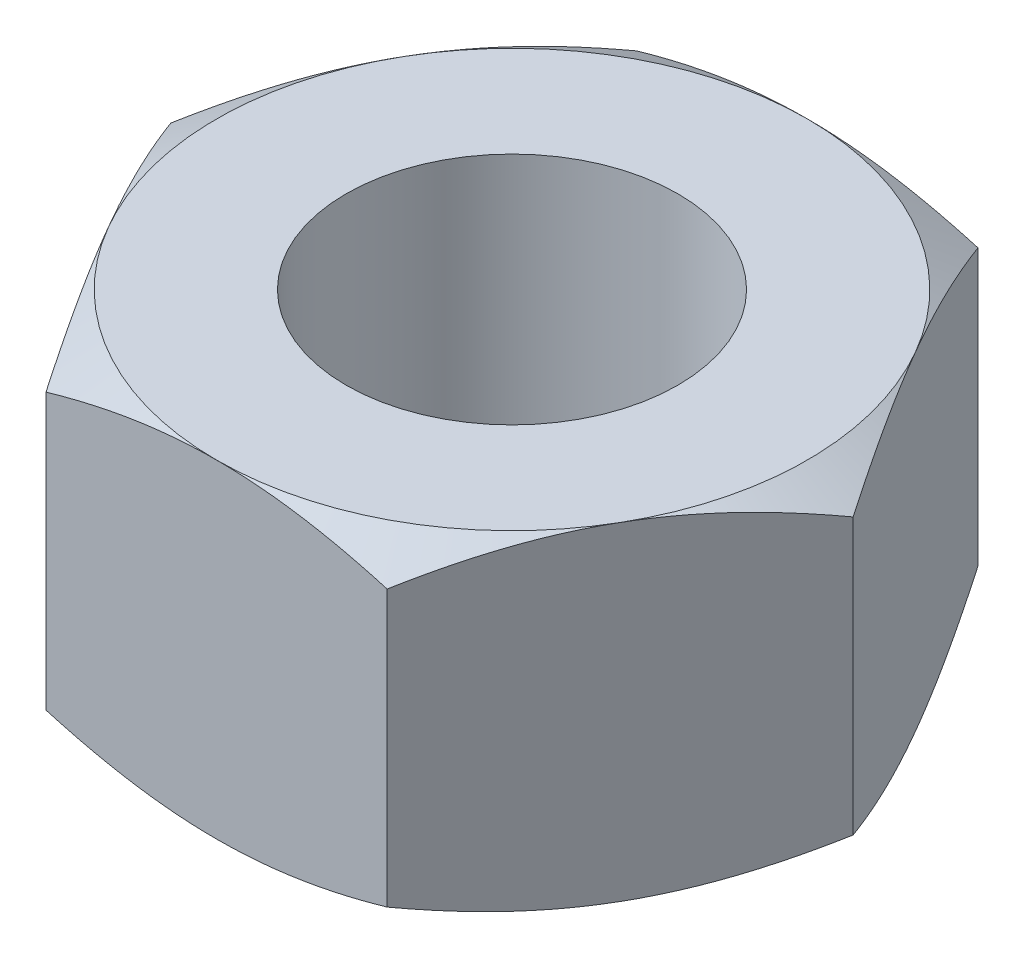
SolidWorks part; units mm, degrees
ref_plane "Front Plane" through (0, 0, 0) normal (0, 0, 1) x (1, 0, 0)
ref_plane "Top Plane" through (0, 0, 0) normal (0, 1, 0) x (1, 0, 0)
ref_plane "Right Plane" through (0, 0, 0) normal (1, 0, 0) x (0, 0, -1)
ref_axis "Axis_X" through (-88.99, 0, 0) along (1, 0, 0)
ref_axis "Axis_Y" through (0, 55, 0) along (0, -1, 0)
ref_axis "Axis_Z" through (0, 0, -88.99) along (0, 0, 1)
sketch "Sketch1" plane through (0, 0, 0) normal (0, 1, 0) x (1, 0, 0)
  line L1 (5.1962, 9) -> (-5.1962, 9)
  line L2 (-5.1962, 9) -> (-10.3923, 0)
  line L3 (-10.3923, 0) -> (-5.1962, -9)
  line L4 (-5.1962, -9) -> (5.1962, -9)
  line L5 (5.1962, -9) -> (10.3923, 0)
  line L6 (10.3923, 0) -> (5.1962, 9)
  circle A0 centre (0, 0) radius 9 construction
  circle A1 centre (0, 0) radius 5.053
  dimension "FIX_4" = 10.106
  dimension "FIX_1" = 18
extrude "Boss-Extrude1" add sketch "Sketch1" along normal blind 10
cosmetic thread "Thread1" parameters "D2"=12
sketch "Sketch2" plane through (0, 0, 0) normal (0, 0, 1) x (1, 0, 0)
  line L0 (-10.3923, 0.8038) -> (-10.3923, 0)
  line L1 (-10.3923, 10) -> (-10.3923, 0) construction
  line L2 (-10.3923, 0) -> (-9, 0)
  line L3 (-5.1962, 0) -> (-10.3923, 0) construction
  line L4 (-9, 0) -> (-10.3923, 0.8038)
  line L7 (-10.3923, 10) -> (-10.3923, 9.1962)
  line L8 (-10.3923, 9.1962) -> (-9, 10)
  line L9 (-10.3923, 10) -> (-5.1962, 10) construction
  line L10 (-10.3923, 10) -> (-9, 10)
  dimension "FIX_5" = 30
revolve "Cut-Revolve1" cut sketch "Sketch2" angle 360 about axis through (0, 55, 0) along (0, -1, 0)
equation "\"Factor\"= 1.082532"
